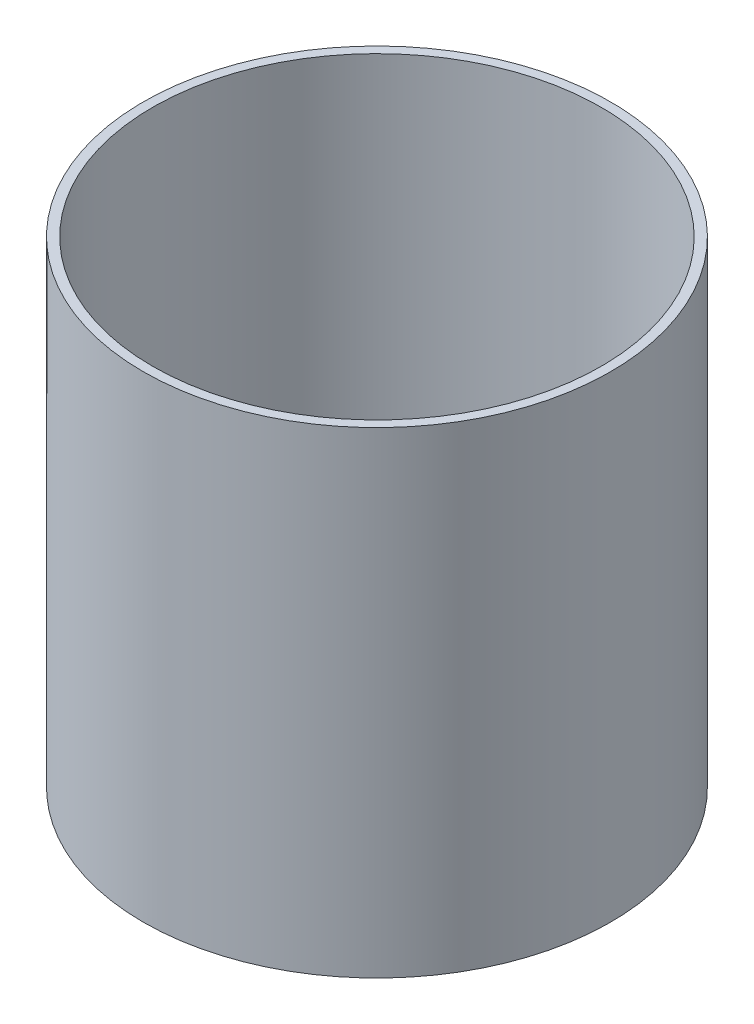
SolidWorks part; units mm, degrees
ref_plane "Front Plane" through (0, 0, 0) normal (0, 0, 1) x (1, 0, 0)
ref_plane "Top Plane" through (0, 0, 0) normal (0, 1, 0) x (1, 0, 0)
ref_plane "Right Plane" through (0, 0, 0) normal (1, 0, 0) x (0, 0, -1)
sketch "Sketch1" plane through (0, 0, 0) normal (0, 1, 0) x (1, 0, 0)
  circle A0 centre (0, 0) radius 50
  dimension "D1" = 100
extrude "Boss-Extrude1" add sketch "Sketch1" along normal blind 2
sketch "Sketch4" plane through (0, 2, 0) normal (0, 1, 0) x (1, 0, 0)
  circle A0 centre (-7.5, 0) radius 2
  circle A1 centre (7.5, 0) radius 2
  dimension "D1" = 4
  dimension "D2" = 4
  dimension "D3" = 7.5
  dimension "D4" = 7.5
extrude "Cut-Extrude1" cut sketch "Sketch4" against normal up to surface (2 mm away) up to face at (0, 0, 50)
sketch "Sketch5" plane through (0, 2, 0) normal (0, 1, 0) x (1, 0, 0)
  circle A0 centre (0, 0) radius 50
  circle A1 centre (0, 0) radius 48
  circle A2 centre (0, 0) radius 50 construction
  dimension "D1" = 2
extrude "Boss-Extrude2" add sketch "Sketch5" along normal blind 100
sketch "Sketch6" plane through (0, 2, 0) normal (0, 1, 0) x (1, 0, 0)
  circle A0 centre (0, 0) radius 2
extrude "Boss-Extrude3" add sketch "Sketch6" along normal blind 20
sketch "Sketch7" plane through (0, 2, 0) normal (0, 1, 0) x (1, 0, 0)
  circle A1 centre (0, -35) radius 3.5
  point P0 (0, 0)
  dimension "D1" = 35
extrude "Cut-Extrude2" cut sketch "Sketch7" against normal blind 5
